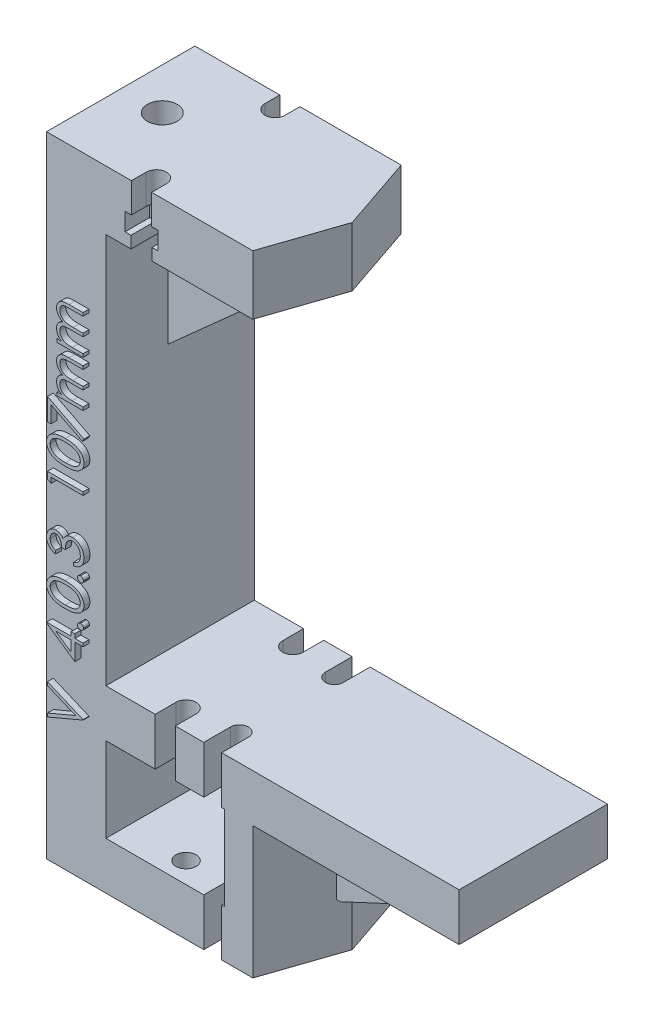
SolidWorks part; units mm, degrees
material "ABS"
ref_plane "Front" through (0, 0, 0) normal (0, 0, 1) x (1, 0, 0)
ref_plane "Top" through (0, 0, 0) normal (0, 1, 0) x (1, 0, 0)
ref_plane "Right" through (0, 0, 0) normal (1, 0, 0) x (0, 0, -1)
sketch "Sketch6" plane through (0, 0, 0) normal (0, 0, 1) x (1, 0, 0)
  line L0 (-25, 53.055) -> (15, 53.055)
  line L1 (15, 53.055) -> (15, 45.055)
  line L2 (15, 45.055) -> (-15, 45.055)
  line L3 (-15, 45.055) -> (-15, -45.055)
  line L4 (-15, -45.055) -> (25, -45.055)
  line L5 (25, -45.055) -> (25, -53.055)
  line L6 (25, -53.055) -> (-25, -53.055)
  line L7 (-25, -53.055) -> (-25, 53.055)
  line L8 (-25, 53.055) -> (25, -53.055) construction
  dimension "D1" = 106.11
  dimension "D2" = 8
  dimension "D4" = 50
  dimension "D5" = 40
extrude "Boss-Extrude2" add sketch "Sketch6" along normal mid plane 25
sketch "Sketch15" plane through (0, 0, 12.5) normal (0, 0, 1) x (1, 0, 0)
  line L0 (-15, -22.805) -> (15, -22.805)
  line L1 (-15, -45.055) -> (-15, 45.055) construction
  line L2 (-15, -30.805) -> (5, -30.805)
  line L3 (5, -53.055) -> (15, -53.055)
  line L4 (15, -53.055) -> (15, -22.805)
  line L5 (-25, -53.055) -> (25, -53.055) construction
  line L6 (-15, -30.805) -> (-15, -22.805)
  line L7 (5, -53.055) -> (5, -30.805)
  dimension "D2" = 8
extrude "Boss-Extrude3" add sketch "Sketch15" against normal up to surface (25 mm away) up to face at (0, 0, -12.5)
sketch "Sketch20" plane through (0, 53.055, 0) normal (0, 1, 0) x (1, 0, 0)
  line L0 (-10.7, 12.5) -> (-10.7, 10)
  line L1 (15, 12.5) -> (-25, 12.5) construction
  line L2 (-7.3, 10) -> (-7.3, 12.5)
  line L3 (-7.3, 12.5) -> (-10.7, 12.5)
  line L4 (0, 0) -> (15, 0) construction
  line L5 (15, -12.5) -> (15, 12.5) construction
  line L6 (-7.3, -12.5) -> (-10.7, -12.5)
  line L7 (-7.3, -10) -> (-7.3, -12.5)
  line L8 (-10.7, -12.5) -> (-10.7, -10)
  line L9 (-9, -10) -> (-9, 10) construction
  arc A0 (-10.7, 10) -> (-7.3, 10) centre (-9, 10) ccw
  arc A1 (-10.7, -10) -> (-7.3, -10) centre (-9, -10) cw
  dimension "D1" = 1.7
  dimension "D2" = 20
extrude "Cut-Extrude2" cut sketch "Sketch20" against normal up to next
sketch "Sketch21" plane through (0, -53.055, 0) normal (0, -1, 0) x (1, 0, 0)
  line L0 (-6.7, 12.5) -> (-6.7, 9)
  line L1 (-25, 12.5) -> (25, 12.5) construction
  line L2 (-3.3, 9) -> (-3.3, 12.5)
  line L3 (-3.3, 12.5) -> (-6.7, 12.5) construction
  line L4 (-5, -9) -> (-5, 9) construction
  line L5 (-6.7, 12.5) -> (-3.3, 12.5)
  line L7 (-3.3, -12.5) -> (-6.7, -12.5)
  line L8 (-3.3, -9) -> (-3.3, -12.5)
  line L9 (-6.7, -12.5) -> (-6.7, -9)
  arc A0 (-6.7, 9) -> (-3.3, 9) centre (-5, 9) ccw
  arc A1 (-6.7, -9) -> (-3.3, -9) centre (-5, -9) cw
  dimension "D1" = 1.7
  dimension "D2" = 18
extrude "Cut-Extrude3" cut sketch "Sketch21" against normal up to surface (30.25 mm away) up to face at (0, -22.805, 0)
sketch "Sketch22" plane through (0, 0, 0) normal (0, 0, 1) x (1, 0, 0)
  line L0 (-15, 21.805) -> (11, 45.055)
  line L1 (-7.3, 45.055) -> (15, 45.055) construction
  line L2 (-15, 45.055) -> (11, 45.055)
  line L5 (-15, -22.805) -> (-15, 45.055) construction
  line L7 (-15, 45.055) -> (-10.7, 45.055) construction
  line L8 (-15, 45.055) -> (-15, 21.805)
extrude "Boss-Extrude5" add sketch "Sketch22" along normal mid plane 4
sketch "Sketch23" plane through (0, 53.055, 0) normal (0, 1, 0) x (1, 0, 0)
  line L0 (-2.51, 12.5) -> (-2.51, 9)
  line L1 (15, 12.5) -> (-7.3, 12.5) construction
  line L2 (0.51, 9) -> (0.51, 12.5)
  line L3 (0.51, 12.5) -> (-2.51, 12.5)
  line L4 (-9, 10) -> (-1, 10) construction
  line L5 (-1, 10) -> (-1, 9) construction
  line L6 (0, 0) -> (12, 0) construction
  line L8 (0.51, -12.5) -> (-2.51, -12.5)
  line L9 (0.51, -9) -> (0.51, -12.5)
  line L10 (-2.51, -12.5) -> (-2.51, -9)
  line L11 (15, -12.5) -> (15, 12.5) construction
  arc A0 (-2.51, 9) -> (0.51, 9) centre (-1, 9) ccw
  arc A1 (-2.51, -9) -> (0.51, -9) centre (-1, -9) cw
  dimension "D1" = 1.51
  dimension "D2" = 8
  dimension "D3" = 1
  dimension "D4" = 3
extrude "Cut-Extrude4" [suppressed] cut sketch "Sketch23" against normal up to next
sketch "Sketch24" plane through (0, -53.055, 0) normal (0, -1, 0) x (1, 0, 0)
  line L0 (1.49, -12.5) -> (1.49, -8)
  line L1 (-3.3, -12.5) -> (25, -12.5) construction
  line L2 (4.51, -8) -> (4.51, -12.5)
  line L3 (4.51, -12.5) -> (1.49, -12.5)
  line L4 (3, -8) -> (3, -9) construction
  line L5 (3, -9) -> (-5, -9) construction
  line L9 (4.51, 12.5) -> (1.49, 12.5)
  line L10 (4.51, 8) -> (4.51, 12.5)
  line L11 (1.49, 12.5) -> (1.49, 8)
  arc A0 (1.49, -8) -> (4.51, -8) centre (3, -8) cw
  arc A1 (1.49, 8) -> (4.51, 8) centre (3, 8) ccw
  dimension "D2" = 8
  dimension "D3" = 1
extrude "Cut-Extrude6" cut sketch "Sketch24" against normal up to surface (30.25 mm away) up to face at (-3.3333, -22.805, 0)
sketch "Sketch28" plane through (0, 53.055, 0) normal (0, 1, 0) x (1, 0, 0)
  line L0 (-10.7, 10) -> (-7.3, 10) construction
  line L1 (-10.7, -10) -> (-7.3, -10) construction
  line L2 (-7.3, -12.5) -> (-7.3, -10) construction
  arc A0 (-10.7, 10) -> (-7.3, 10) centre (-9, 10) ccw construction
  arc A1 (-7.3, -10) -> (-10.7, -10) centre (-9, -10) ccw construction
sketch "Sketch29" plane through (-25, 0, 0) normal (-1, 0, 0) x (0, 0, 1)
  line L0 (-12.5, 53.055) -> (12.5, 53.055)
  line L1 (12.5, 53.055) -> (12.5, -53.055)
  line L2 (12.5, -53.055) -> (-12.9424, -53.055)
  line L3 (-12.9424, -53.055) -> (-12.5, 53.055)
extrude "Cut-Extrude7" [suppressed] cut sketch "Sketch29" against normal blind 6
sketch "Sketch30" plane through (0, -45.055, 0) normal (0, 1, 0) x (1, 0, 0)
  line L0 (25, 12.5) -> (25, -12.5)
  line L1 (25, -12.5) -> (15, -12.5)
  line L2 (15, -12.5) -> (15, 12.5)
  line L3 (15, 12.5) -> (25, 12.5)
extrude "Cut-Extrude8" cut sketch "Sketch30" against normal up to surface (8 mm away) up to face at (-0.8, -53.055, 0)
sketch "Sketch34" plane through (0, -22.805, 0) normal (0, 1, 0) x (1, 0, 0)
  line L1 (9.755, 12.5) -> (14, 0)
  line L2 (15, -12.5) -> (4.51, -12.5) construction
  line L3 (9.755, -12.5) -> (15, -12.5)
  line L6 (15, 12.5) -> (9.755, 12.5)
  line L7 (15, 12.5) -> (4.51, 12.5) construction
  line L9 (15, -12.5) -> (15, 12.5)
  line L10 (15, 0) -> (14, 0) construction
  line L11 (14, 0) -> (9.755, -12.5)
extrude "Cut-Extrude9" cut sketch "Sketch34" against normal through all both and the other way through all
sketch "Sketch35" plane through (0, 0, 12.5) normal (0, 0, 1) x (1, 0, 0)
  line L0 (-17.85, 53.055) -> (-17.85, -53.055) construction
  line L1 (-10.7, 53.055) -> (-25, 53.055) construction
  line L2 (-25, -53.055) -> (-6.7, -53.055) construction
  text T0 "V  4.0.3  107mm" font "Century Gothic" height 6
extrude "Boss-Extrude6" add sketch "Sketch35" along normal blind 1
sketch3d "3DSketch1"
  line L0 (4.51, -22.805, 12.5) -> (4.51, -30.805, 12.5)
  line L1 (4.51, -30.805, 12.5) -> (4.51, -30.805, -12.5)
  line L2 (4.51, -30.805, -12.5) -> (4.51, -22.805, -12.5)
  line L3 (4.51, -22.805, -12.5) -> (4.51, -22.805, 12.5)
extrude "Boss-Extrude7" add sketch "3DSketch1" along direction (1, 0, 0) on the side against the normal blind 40
sketch "Sketch37" plane through (0, 0, 0) normal (0, 0, 1) x (1, 0, 0)
  line L1 (14, -30.805) -> (44.51, -30.805)
  line L3 (5, -45.055) -> (14, -45.055) construction
  line L4 (14, -30.805) -> (14, -45.055)
  line L5 (14, -45.055) -> (44.51, -30.805)
extrude "Boss-Extrude17" add sketch "Sketch37" along direction (0, 0, 1) on the side of the normal mid plane 4 separate body
sketch "Sketch38" plane through (0, 45.055, 0) normal (0, -1, 0) x (1, 0, 0)
  line L0 (-11.75, 11.5877) -> (-11.75, 12.5) construction
  line L1 (-10.7, 10) -> (-7.3, 10) construction
  line L2 (-6.25, 8.4123) -> (-6.25, 11.5877) construction
  line L3 (-9, 6.8246) -> (-6.25, 8.4123)
  line L4 (-11.75, 8.4123) -> (-9, 6.8246)
  line L5 (-11.75, 11.5877) -> (-11.75, 8.4123) construction
  line L6 (-9, 13.1754) -> (-11.75, 11.5877) construction
  line L7 (-6.25, 11.5877) -> (-9, 13.1754) construction
  line L8 (-10.7, -10) -> (-7.3, -10) construction
  line L9 (-6.25, -11.5877) -> (-6.25, -8.4123) construction
  line L10 (-6.25, -8.4123) -> (-9, -6.8246)
  line L11 (-9, -6.8246) -> (-11.75, -8.4123)
  line L12 (-11.75, -8.4123) -> (-11.75, -11.5877) construction
  line L13 (-11.75, -11.5877) -> (-9, -13.1754) construction
  line L14 (-9, -13.1754) -> (-6.25, -11.5877) construction
  line L15 (-15, 12.5) -> (-10.7, 12.5) construction
  line L17 (-7.3, 12.5) -> (9.755, 12.5) construction
  line L18 (-6.25, 12.5) -> (-6.25, 11.5877) construction
  line L19 (-11.75, -11.5877) -> (-11.75, -12.5) construction
  line L20 (-15, -12.5) -> (-10.7, -12.5) construction
  line L21 (-11.77, -12.5) -> (-6.23, -12.5)
  line L22 (-7.3, -12.5) -> (9.755, -12.5) construction
  line L23 (-6.25, -12.5) -> (-6.25, -11.5877) construction
  line L24 (-11.77, 12.5) -> (-11.77, 8.4238)
  line L25 (-11.77, 8.4238) -> (-11.75, 8.4123)
  line L26 (-6.23, 12.5) -> (-6.23, 8.4238)
  line L27 (-6.23, 8.4238) -> (-6.25, 8.4123)
  line L28 (-11.77, 12.5) -> (-6.23, 12.5)
  line L29 (-6.25, -8.4123) -> (-6.23, -8.4238)
  line L30 (-6.23, -8.4238) -> (-6.23, -12.5)
  line L31 (-11.77, -12.5) -> (-11.77, -8.4238)
  line L32 (-11.77, -8.4238) -> (-11.75, -8.4123)
  circle A1 centre (-9, 10) radius 2.75 construction
  circle A2 centre (-9, 10) radius 3.1754 construction
  circle A3 centre (-9, -10) radius 3.1754 construction
  circle A4 centre (-9, -10) radius 2.75 construction
  point P18 (-6.25, -10)
  point P19 (-9, 10)
  point P24 (-7.625, -7.6184)
  point P25 (-10.375, -7.6184)
  point P42 (-11.75, 12.0439)
  dimension "D1" = 5.5
  dimension "D2" = 6
  dimension "D3" = 6.3509
  dimension "D4" = 5.5
  dimension "D5" = 6.3509
  dimension "D6" = 0.02
  dimension "D7" = 0.02
  dimension "D8" = 0.02
  dimension "D9" = 0.02
extrude "Cut-Extrude10" cut sketch "Sketch38" against normal blind 3
sketch "Sketch39" plane through (14, 0, 0) normal (-1, 0, 0) x (0, 0, 1)
  line L1 (-2, -45.055) -> (2, -45.055)
  line L2 (-2, -45.055) -> (-2, -30.805)
  line L3 (-2, -30.805) -> (2, -30.805)
  line L4 (2, -45.055) -> (2, -30.805)
extrude "Boss-Extrude18" add sketch "Sketch39" along normal blind 2.5
hole_wizard "Ø5.0mm Dowel Hole1" positions "Sketch41" profile "Sketch42" hole size "Ø5.0" standard "ANSI Metric"
sketch "Sketch41" plane through (0, 53.055, 0) normal (0, 1, 0) x (1, 0, 0)
  line L0 (-25, 0) -> (-18, 0) construction
  line L1 (-25, -12.5) -> (-25, 12.5) construction
  point P0 (-18, 0)
  dimension "D1" = 7
sketch "Sketch42" plane through (-18, 53.055, 0) normal (1, 0, 0) x (0, 0, 1)
  line L0 (0, 0) -> (0, 6.5022)
  line L1 (0, 6.5022) -> (2.5, 5)
  line L2 (2.5, 5) -> (2.5, 0)
  line L5 (2.5, 0) -> (0, 0)
  line L10 (0, 6.5022) -> (-2.5, 5) construction
  line L11 (0, -6.35) -> (0, 107.95) construction
  dimension "Hole Dia." = 5
  dimension "Hole Depth" = 5
  dimension "Drill Angle" = 118
sketch "Sketch43" plane through (0, 45.055, 0) normal (0, -1, 0) x (1, 0, 0)
  line L0 (-11.77, 12.5) -> (-10.77, 12.5)
  line L1 (-10.77, 12.5) -> (-10.77, 7.8465)
  line L2 (-6.23, 12.5) -> (-7.23, 12.5)
  line L3 (-7.23, 12.5) -> (-7.23, 7.8465)
  line L4 (-11.77, -12.5) -> (-10.77, -12.5)
  line L5 (-10.77, -12.5) -> (-10.77, -7.8465)
  line L6 (-6.23, -12.5) -> (-7.23, -12.5)
  line L7 (-7.23, -12.5) -> (-7.23, -7.8465)
  line L8 (5, 2) -> (5, -2)
  line L19 (-15, -12.5) -> (-11.77, -12.5)
  line L20 (-11.77, 8.4238) -> (-11.77, 12.5)
  line L21 (-11.77, -8.4238) -> (-9, -6.8246)
  line L22 (-9, -6.8246) -> (-6.23, -8.4238)
  line L23 (-11.77, 8.4238) -> (-11.77, 12.5)
  line L24 (-6.23, -12.5) -> (9.755, -12.5)
  line L25 (9.755, -12.5) -> (14, 0)
  line L26 (14, 0) -> (9.755, 12.5)
  line L27 (9.755, 12.5) -> (-6.23, 12.5)
  line L28 (-11.77, -12.5) -> (-11.77, -8.4238)
  line L29 (-6.23, 8.4238) -> (-9, 6.8246)
  line L30 (-9, 6.8246) -> (-11.77, 8.4238)
  line L31 (-11.77, -12.5) -> (-11.77, -8.4238)
  line L32 (-11.77, 12.5) -> (-15, 12.5)
  line L33 (-15, 12.5) -> (-15, 2)
  line L34 (-15, 2) -> (11, 2)
  line L35 (11, 2) -> (11, -2)
  line L36 (11, -2) -> (-15, -2)
  line L37 (-15, -2) -> (-15, -12.5)
  line L38 (-15, -12.5) -> (-11.77, -12.5)
  line L40 (-11.77, -8.4238) -> (-9, -6.8246)
  line L41 (-9, -6.8246) -> (-6.23, -8.4238)
  line L43 (-6.23, -12.5) -> (9.755, -12.5)
  line L44 (9.755, -12.5) -> (14, 0)
  line L45 (14, 0) -> (9.755, 12.5)
  line L46 (9.755, 12.5) -> (-6.23, 12.5)
  line L48 (-6.23, 8.4238) -> (-9, 6.8246)
  line L49 (-9, 6.8246) -> (-11.77, 8.4238)
  line L51 (-11.77, 12.5) -> (-15, 12.5)
  line L52 (-15, 12.5) -> (-15, 2)
  line L53 (-15, 2) -> (11, 2)
  line L54 (11, 2) -> (11, -2)
  line L55 (11, -2) -> (-15, -2)
  line L56 (-15, -2) -> (-15, -12.5)
  line L57 (-6.23, -8.4238) -> (-6.23, -12.5)
  line L58 (-6.23, -8.4238) -> (-6.23, -12.5)
  line L59 (-6.23, 12.5) -> (-6.23, 8.4238)
  line L60 (-6.23, 12.5) -> (-6.23, 8.4238)
  line M22 (-11.77, -8.4238) -> (-9, -6.8246)
  line M23 (-9, -6.8246) -> (-6.23, -8.4238)
  line M30 (-6.23, 8.4238) -> (-9, 6.8246)
  line M31 (-9, 6.8246) -> (-11.77, 8.4238)
  line M35 (-15, 2) -> (11, 2)
  line M36 (11, 2) -> (11, -2)
  line M37 (11, -2) -> (-15, -2)
  line M39 (-11.77, 8.4238) -> (-11.77, 12.5)
  line M40 (-11.77, -12.5) -> (-11.77, -8.4238)
  line M41 (-6.23, -8.4238) -> (-6.23, -12.5)
  line M42 (-6.23, 12.5) -> (-6.23, 8.4238)
  dimension "D2" = 1
  dimension "D3" = 1
  dimension "D4" = 1
  dimension "D5" = 1
  dimension "D6" = 6
  dimension "D1" = 0
extrude "Boss-Extrude19" add sketch "Sketch43" along normal blind 2 contours L8 M35 M37 M36 | L1 L0 M39 M31 | L2 L3 M30 M42 | L4 L5 M22 M40 | L7 L6 M41 M23 | L38 L31 L40 L41 L58 L43 L44 L45 L46 L60 L48 L49 L23 L51 L52 L53 L54 L55 L56
sketch "Sketch44" plane through (0, -53.055, 0) normal (0, -1, 0) x (1, 0, 0)
  line L0 (-6.7, -9) -> (-6.7, -12.5)
  line L1 (-6.7, -12.5) -> (-3.3, -12.5)
  line L2 (-3.3, -12.5) -> (-3.3, -9)
  line L3 (-6.7, 9) -> (-6.7, 12.5)
  line L4 (-6.7, 12.5) -> (-3.3, 12.5)
  line L5 (-3.3, 12.5) -> (-3.3, 9)
  circle A0 centre (-5, -9) radius 1.7
  circle A1 centre (-5, 9) radius 1.7
  line M8 (-3.3, 12.5) -> (-3.3, 9)
  line M10 (-6.7, 9) -> (-6.7, 12.5)
  line M14 (-6.7, -12.5) -> (-6.7, -9)
  line M16 (-3.3, -9) -> (-3.3, -12.5)
extrude "Boss-Extrude20" add sketch "Sketch44" against normal up to surface (8 mm away) contours A1 L4 M8 M10 | A0 L1 M14 M16
